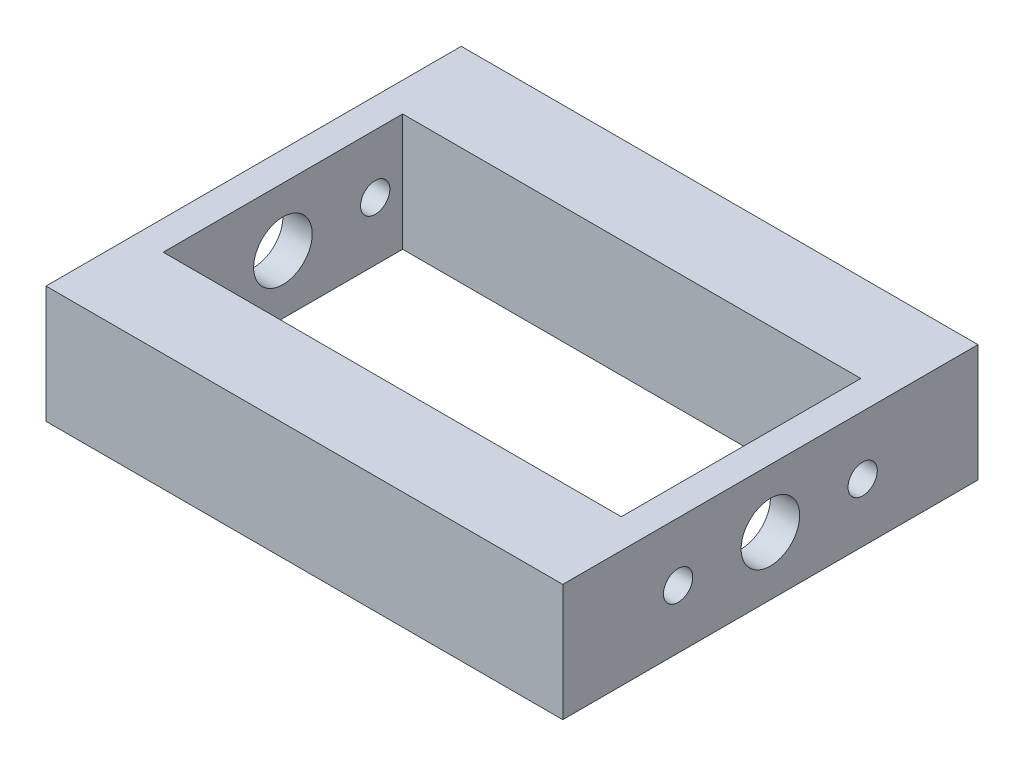
SolidWorks part; units mm, degrees
material "AISI 1020"
ref_plane "Alzado" through (0, 0, 0) normal (0, 0, 1) x (1, 0, 0)
ref_plane "Planta" through (0, 0, 0) normal (0, 1, 0) x (1, 0, 0)
ref_plane "Vista lateral" through (0, 0, 0) normal (1, 0, 0) x (0, 0, -1)
sketch "Croquis1" plane through (0, 0, 0) normal (0, 1, 0) x (1, 0, 0)
  line L1 (75.05, -45) -> (-75.05, -45)
  line L2 (75.05, -45) -> (75.05, 45)
  line L3 (75.05, 45) -> (-75.05, 45)
  line L4 (-75.05, -45) -> (-75.05, 45)
  line L5 (75.05, -45) -> (-75.05, 45) construction
  line L6 (75.05, 45) -> (-75.05, -45) construction
  line L7 (36.95, -25.95) -> (-36.95, -25.95) construction
  line L8 (49.65, -13.25) -> (49.65, 13.25) construction
  line L9 (36.95, 25.95) -> (-36.95, 25.95) construction
  line L10 (-49.65, -13.25) -> (-49.65, 13.25) construction
  line L11 (49.65, -25.95) -> (-49.65, 25.95) construction
  line L12 (49.65, 25.95) -> (-49.65, -25.95) construction
  line L13 (-49.65, -25.95) -> (49.65, -25.95)
  line L14 (-49.65, -25.95) -> (-49.65, 25.95)
  line L15 (-49.65, 25.95) -> (49.65, 25.95)
  line L16 (49.65, -25.95) -> (49.65, 25.95)
  arc A0 (36.95, -25.95) -> (49.65, -13.25) centre (36.95, -13.25) ccw construction
  arc A1 (49.65, 13.25) -> (36.95, 25.95) centre (36.95, 13.25) ccw construction
  arc A2 (-36.95, 25.95) -> (-49.65, 13.25) centre (-36.95, 13.25) ccw construction
  arc A3 (-36.95, -25.95) -> (-49.65, -13.25) centre (-36.95, -13.25) cw construction
  point P0 (0, 0)
  point P6 (0, 0)
  dimension "D5" = 12.7
  dimension "D1" = 150.1
  dimension "D2" = 90
  dimension "D3" = 19.05
  dimension "D4" = 25.4
extrude "Saliente-Extruir1" add sketch "Croquis1" along normal blind 25.4
sketch "Croquis2" plane through (75.05, 0, 0) normal (1, 0, 0) x (0, 0, -1)
  line L0 (0, 0) -> (0, 12.7) construction
  circle A0 centre (0, 12.7) radius 6.35
  dimension "D2" = 12.7
  dimension "D1" = 12.7
extrude "Saliente-Extruir2" add sketch "Croquis2" along normal blind 51.85
extrude "Saliente-Extruir3" add sketch "Croquis2<2>" against normal blind 24.05 from surface starting at face at (-75.05, 12.7, 0)
sketch "Croquis2<2>" plane through (75.05, 0, 0) normal (1, 0, 0) x (0, 0, -1) same geometry as "Croquis2"
sketch "Croquis3" plane through (-75.05, 0, 0) normal (-1, 0, 0) x (0, 0, 1)
  line L0 (-45, 25.4) -> (-45, 0) construction
  circle A0 centre (0, 12.7) radius 45
  circle A1 centre (0, 12.7) radius 65
  dimension "D1" = 20
extrude "Cortar-Extruir1" [suppressed] cut sketch "Croquis3" against normal through all
sketch "Croquis4" plane through (75.05, 0, 0) normal (1, 0, 0) x (0, 0, -1)
  line L0 (-20, 12.7) -> (20, 12.7) construction
  line L1 (0, 0) -> (0, 12.7) construction
  circle A0 centre (-20, 12.7) radius 3.175
  circle A1 centre (20, 12.7) radius 3.175
  circle A2 centre (0, 12.7) radius 6.35 construction
  dimension "D1" = 6.35
  dimension "D2" = 40
extrude "Cortar-Extruir2" cut sketch "Croquis4" against normal through all
sketch "Croquis5" [suppressed] plane through (0, 25.4, 0) normal (0, 1, 0) x (1, 0, 0)
  line L0 (-75, 55.721) -> (-75, -55.721) construction
  line L1 (75, -55.721) -> (-75, -55.721)
  line L2 (75, -55.721) -> (75, -42.15)
  line L3 (75, -42.15) -> (-75, -42.15)
  line L4 (-75, -55.721) -> (-75, -42.15)
  line L5 (-36.9, -42.15) -> (36.9, -42.15) construction
extrude "Saliente-Extruir4" [suppressed] add sketch "Croquis5" along normal blind 0.5
fillet "Redondeo1" [suppressed] radius 5
fillet "Redondeo2" [suppressed] radius 5
extrude "Cortar-Extruir3" cut sketch "Croquis2<3>" against normal through all from surface starting at face at (126.9, 12.7, -6.35)
sketch "Croquis2<3>" plane through (75.05, 0, 0) normal (1, 0, 0) x (0, 0, -1) same geometry as "Croquis2"
sketch "Croquis6" plane through (0, 25.4, 0) normal (0, 1, 0) x (1, 0, 0)
  line L0 (75.05, 45) -> (-75.05, 45) construction
  line L1 (-75.05, -45) -> (-56, -45)
  line L2 (-75.05, -45) -> (-75.05, 45)
  line L3 (-75.05, 45) -> (-56, 45)
  line L4 (-56, -45) -> (-56, 45)
  line L6 (75.05, -45) -> (56, -45)
  line L7 (75.05, -45) -> (75.05, 45)
  line L8 (75.05, 45) -> (56, 45)
  line L9 (56, -45) -> (56, 45)
  dimension "D1" = 19.05
extrude "Cortar-Extruir4" cut sketch "Croquis6" against normal through all
sketch "Croquis7" plane through (0, 25.4, 0) normal (0, 1, 0) x (1, 0, 0)
  line L0 (56, 45) -> (56, -45) construction
  line L1 (-56, -45) -> (56, -45)
  line L2 (-56, -45) -> (-56, -47.9795)
  line L3 (-56, -47.9795) -> (56, -47.9795)
  line L4 (56, -45) -> (56, -47.9795)
extrude "Saliente-Extruir5" [suppressed] add sketch "Croquis7" along normal blind 0.5
sketch "Croquis8" plane through (0, 25.4, 0) normal (0, 1, 0) x (1, 0, 0)
  line L0 (-16.055, -25.95) -> (-16.055, -45)
  line L1 (-49.65, -25.95) -> (49.65, -25.95) construction
  line L2 (-56, -45) -> (56, -45) construction
  line L3 (-16.055, -45) -> (15.3569, -45)
  line L4 (15.3569, -45) -> (15.3569, -25.95)
  line L5 (15.3569, -25.95) -> (-16.055, -25.95)
extrude "Saliente-Extruir6" [suppressed] add sketch "Croquis8" along normal blind 0.2
fillet "Redondeo3" [suppressed] radius 6.35
